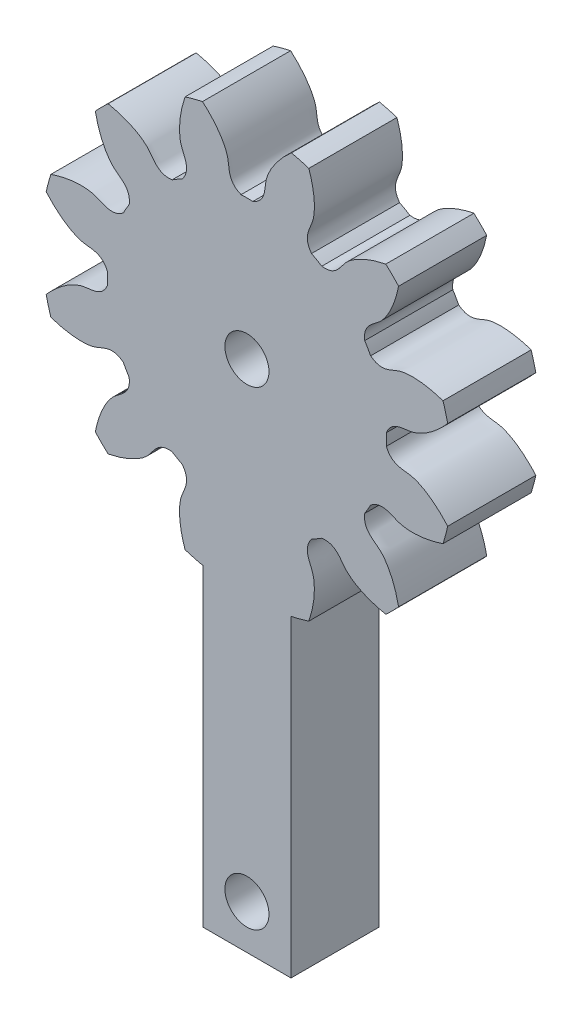
SolidWorks part; units mm, degrees
ref_plane "前视基准面" through (0, 0, 0) normal (0, 0, 1) x (1, 0, 0)
ref_plane "上视基准面" through (0, 0, 0) normal (0, 1, 0) x (1, 0, 0)
ref_plane "右视基准面" through (0, 0, 0) normal (1, 0, 0) x (0, 0, -1)
sketch "草图1" plane through (0, 0, 0) normal (0, 0, 1) x (1, 0, 0)
  circle A0 centre (0, 0) radius 14
extrude "凸台-拉伸1" add sketch "草图1" along normal blind 30
ref_axis "基准轴1" through (0, 0, -1.5) along (0, 0, 1)
sketch "草图2" plane through (0, 0, 0) normal (0, 0, 1) x (1, 0, 0)
  line L0 (0, 0) -> (0, 14) construction
  circle A0 centre (0, 0) radius 14 construction
  arc A1 (0.4017, 9.4915) -> (-0.4017, 9.4915) centre (0, 0) ccw
  arc A2 (6.9952, 15.7899) -> (-6.9952, 15.7899) centre (0, 0) ccw
  spline S0 degree 3 poles (0.4017, 9.4915) (1.3616, 9.8986) (1.1487, 10.6896) (1.3523, 11.379) (1.3652, 11.4198) (1.3805, 11.4647) (1.3981, 11.5135) (1.4183, 11.5661) (1.4413, 11.6225) (1.4671, 11.6826) (1.4961, 11.7462) (1.5282, 11.8133) (1.5637, 11.8838) (1.6028, 11.9576) (1.6455, 12.0345) (1.6919, 12.1144) (1.7423, 12.1973) (1.7968, 12.2829) (1.8555, 12.3712) (1.9185, 12.462) (1.9859, 12.5552) (2.0579, 12.6506) (2.1346, 12.7481) (2.2161, 12.8475) (2.3025, 12.9487) (2.3939, 13.0516) (2.4904, 13.1559) (2.5921, 13.2615) (2.6991, 13.3682) (2.8114, 13.4759) (2.9292, 13.5844) (3.0525, 13.6935) (3.1814, 13.803) (3.316, 13.9128) (3.4563, 14.0226) (3.6023, 14.1323) (3.7542, 14.2418) (3.912, 14.3507) (4.0756, 14.4589) (4.2452, 14.5663) (4.4208, 14.6726) (4.6024, 14.7776) (4.79, 14.8811) (4.9836, 14.983) (5.1832, 15.083) (5.3889, 15.1809) (5.6006, 15.2765) (5.8183, 15.3697) (6.042, 15.4602) (6.2717, 15.5478) (6.5888, 15.6615) (6.8312, 15.7402) (6.9952, 15.7899) knots 0 0 0 0 0.218015 0.222044 0.226546 0.231522 0.236972 0.242897 0.249295 0.256167 0.263513 0.271332 0.279626 0.288394 0.297636 0.307351 0.317541 0.328204 0.339341 0.350953 0.363038 0.375597 0.38863 0.402137 0.416118 0.430573 0.445502 0.460904 0.476781 0.493132 0.509956 0.527255 0.545027 0.563273 0.581994 0.601188 0.620856 0.640998 0.661614 0.682704 0.704268 0.726305 0.748817 0.771803 0.795262 0.819196 0.843603 0.868484 0.89384 0.919669 0.945972 1 1 1 1
  spline S1 degree 3 poles (-0.4017, 9.4915) (-1.3616, 9.8986) (-1.1487, 10.6896) (-1.3523, 11.379) (-1.3652, 11.4198) (-1.3805, 11.4647) (-1.3981, 11.5135) (-1.4183, 11.5661) (-1.4413, 11.6225) (-1.4671, 11.6826) (-1.4961, 11.7462) (-1.5282, 11.8133) (-1.5637, 11.8838) (-1.6028, 11.9576) (-1.6455, 12.0345) (-1.6919, 12.1144) (-1.7423, 12.1973) (-1.7968, 12.2829) (-1.8555, 12.3712) (-1.9185, 12.462) (-1.9859, 12.5552) (-2.0579, 12.6506) (-2.1346, 12.7481) (-2.2161, 12.8475) (-2.3025, 12.9487) (-2.3939, 13.0516) (-2.4904, 13.1559) (-2.5921, 13.2615) (-2.6991, 13.3682) (-2.8114, 13.4759) (-2.9292, 13.5844) (-3.0525, 13.6935) (-3.1814, 13.803) (-3.316, 13.9128) (-3.4563, 14.0226) (-3.6023, 14.1323) (-3.7542, 14.2418) (-3.912, 14.3507) (-4.0756, 14.4589) (-4.2452, 14.5663) (-4.4208, 14.6726) (-4.6024, 14.7776) (-4.79, 14.8811) (-4.9836, 14.983) (-5.1832, 15.083) (-5.3889, 15.1809) (-5.6006, 15.2765) (-5.8183, 15.3697) (-6.042, 15.4602) (-6.2717, 15.5478) (-6.5888, 15.6615) (-6.8312, 15.7402) (-6.9952, 15.7899) knots 0 0 0 0 0.218015 0.222044 0.226546 0.231522 0.236972 0.242897 0.249295 0.256167 0.263513 0.271332 0.279626 0.288394 0.297636 0.307351 0.317541 0.328204 0.339341 0.350953 0.363038 0.375597 0.38863 0.402137 0.416118 0.430573 0.445502 0.460904 0.476781 0.493132 0.509956 0.527255 0.545027 0.563273 0.581994 0.601188 0.620856 0.640998 0.661614 0.682704 0.704268 0.726305 0.748817 0.771803 0.795262 0.819196 0.843603 0.868484 0.89384 0.919669 0.945972 1 1 1 1
extrude "切除-拉伸1" cut sketch "草图2" along normal through all
pattern_circular "阵列(圆周)1" count 12 every 30 about axis through (0, 0, -1.5) along (0, 0, 1) of "切除-拉伸1"
sketch "草图3" plane through (0, 0, 0) normal (0, 0, 1) x (1, 0, 0)
  circle A0 centre (0, 0) radius 12 construction
  dimension "Dn" = 24
sketch "草图4" plane through (0, 0, 30) normal (0, 0, 1) x (1, 0, 0)
  arc A24 (-4.3979, 8.4207) -> (-5.0936, 8.019) centre (0, 0) ccw
  arc A25 (-9.4547, 10.3251) -> (-10.3251, 9.4547) centre (0, 0) ccw
  arc A26 (-8.019, 5.0936) -> (-8.4207, 4.3979) centre (0, 0) ccw
  arc A27 (-13.3506, 4.2145) -> (-13.6692, 3.0255) centre (0, 0) ccw
  arc A28 (-9.4915, 0.4017) -> (-9.4915, -0.4017) centre (0, 0) ccw
  arc A29 (-13.6692, -3.0255) -> (-13.3506, -4.2145) centre (0, 0) ccw
  arc A30 (-8.4207, -4.3979) -> (-8.019, -5.0936) centre (0, 0) ccw
  arc A31 (-10.3251, -9.4547) -> (-9.4547, -10.3251) centre (0, 0) ccw
  arc A32 (-5.0936, -8.019) -> (-4.3979, -8.4207) centre (0, 0) ccw
  arc A33 (-4.2145, -13.3506) -> (-3.0255, -13.6692) centre (0, 0) ccw
  arc A34 (-0.4017, -9.4915) -> (0.4017, -9.4915) centre (0, 0) ccw
  arc A35 (3.0255, -13.6692) -> (4.2145, -13.3506) centre (0, 0) ccw
  arc A36 (4.3979, -8.4207) -> (5.0936, -8.019) centre (0, 0) ccw
  arc A37 (9.4547, -10.3251) -> (10.3251, -9.4547) centre (0, 0) ccw
  arc A38 (8.019, -5.0936) -> (8.4207, -4.3979) centre (0, 0) ccw
  arc A39 (13.3506, -4.2145) -> (13.6692, -3.0255) centre (0, 0) ccw
  arc A40 (9.4915, -0.4017) -> (9.4915, 0.4017) centre (0, 0) ccw
  arc A41 (13.6692, 3.0255) -> (13.3506, 4.2145) centre (0, 0) ccw
  arc A42 (8.4207, 4.3979) -> (8.019, 5.0936) centre (0, 0) ccw
  arc A43 (10.3251, 9.4547) -> (9.4547, 10.3251) centre (0, 0) ccw
  arc A44 (5.0936, 8.019) -> (4.3979, 8.4207) centre (0, 0) ccw
  arc A45 (4.2145, 13.3506) -> (3.0255, 13.6692) centre (0, 0) ccw
  arc A46 (0.4017, 9.4915) -> (-0.4017, 9.4915) centre (0, 0) ccw
  arc A47 (-3.0255, 13.6692) -> (-4.2145, 13.3506) centre (0, 0) ccw
  arc A48 (-4.3979, 8.4207) -> (-5.0936, 8.019) centre (0, 0) ccw
  arc A49 (-9.4547, 10.3251) -> (-10.3251, 9.4547) centre (0, 0) ccw
  arc A50 (-8.019, 5.0936) -> (-8.4207, 4.3979) centre (0, 0) ccw
  arc A51 (-13.3506, 4.2145) -> (-13.6692, 3.0255) centre (0, 0) ccw
  arc A52 (-9.4915, 0.4017) -> (-9.4915, -0.4017) centre (0, 0) ccw
  arc A53 (-13.6692, -3.0255) -> (-13.3506, -4.2145) centre (0, 0) ccw
  arc A54 (-8.4207, -4.3979) -> (-8.019, -5.0936) centre (0, 0) ccw
  arc A55 (-10.3251, -9.4547) -> (-9.4547, -10.3251) centre (0, 0) ccw
  arc A56 (-5.0936, -8.019) -> (-4.3979, -8.4207) centre (0, 0) ccw
  arc A57 (-4.2145, -13.3506) -> (-3.0255, -13.6692) centre (0, 0) ccw
  arc A58 (-0.4017, -9.4915) -> (0.4017, -9.4915) centre (0, 0) ccw
  arc A59 (3.0255, -13.6692) -> (4.2145, -13.3506) centre (0, 0) ccw
  arc A60 (4.3979, -8.4207) -> (5.0936, -8.019) centre (0, 0) ccw
  arc A61 (9.4547, -10.3251) -> (10.3251, -9.4547) centre (0, 0) ccw
  arc A62 (8.019, -5.0936) -> (8.4207, -4.3979) centre (0, 0) ccw
  arc A63 (13.3506, -4.2145) -> (13.6692, -3.0255) centre (0, 0) ccw
  arc A64 (9.4915, -0.4017) -> (9.4915, 0.4017) centre (0, 0) ccw
  arc A65 (13.6692, 3.0255) -> (13.3506, 4.2145) centre (0, 0) ccw
  arc A66 (8.4207, 4.3979) -> (8.019, 5.0936) centre (0, 0) ccw
  arc A67 (10.3251, 9.4547) -> (9.4547, 10.3251) centre (0, 0) ccw
  arc A68 (5.0936, 8.019) -> (4.3979, 8.4207) centre (0, 0) ccw
  arc A69 (4.2145, 13.3506) -> (3.0255, 13.6692) centre (0, 0) ccw
  arc A70 (0.4017, 9.4915) -> (-0.4017, 9.4915) centre (0, 0) ccw
  arc A71 (-3.0255, 13.6692) -> (-4.2145, 13.3506) centre (0, 0) ccw
  spline S24 degree 3 poles (2734.3549, 2922.0708) (-47.5679, -59.6433) (0.0383, 2.6205) (-6.8721, 9.1892) (-6.9309, 9.2418) (-7.0145, 9.3106) (-7.1151, 9.387) (-7.2335, 9.4697) (-7.3702, 9.5573) (-7.5259, 9.6485) (-7.7011, 9.7419) (-7.8961, 9.8361) (-8.1112, 9.9296) (-8.3468, 10.021) (-8.6028, 10.1087) (-8.8795, 10.1914) (-41.9256, 18.6379) (-125.0183, -186.7572) (3142.6374, 2471.5878) knots -2.297192 -2.297192 -2.297192 -2.297192 0.69442 0.698448 0.707927 0.719301 0.732571 0.747737 0.764798 0.783756 0.804608 0.827357 0.852001 0.878542 0.906977 0.937309 0.969536 11.65638 11.65638 11.65638 11.65638 only from (-5.0936, 8.019) to (-9.4547, 10.3251)
  spline S25 degree 3 poles (-2465.1384, -3147.6919) (184.2368, 127.601) (-19.1156, 41.103) (-10.1508, 8.7386) (-10.0654, 8.4722) (-9.9757, 8.2264) (-9.883, 8.0011) (-9.789, 7.7961) (-9.695, 7.6111) (-9.6025, 7.4457) (-9.5129, 7.2995) (-9.4276, 7.172) (-9.359, 7.0778) (-9.2968, 6.9977) (-9.2418, 6.9309) (-9.1892, 6.8721) (-2.6206, -0.0382) (59.6418, 47.5668) (-2921.9619, -2734.2533) knots -10.476322 -10.476322 -10.476322 -10.476322 0.046814 0.078094 0.107478 0.134965 0.160558 0.184254 0.206055 0.22596 0.243969 0.260083 0.274301 0.280699 0.292073 0.301552 0.30558 3.297155 3.297155 3.297155 3.297155 only from (-10.3251, 9.4547) to (-8.019, 5.0936)
  spline S26 degree 3 poles (906.9854, 3897.7649) (-11.3733, -75.4366) (-1.2771, 2.2886) (-10.546, 4.522) (-10.6233, 4.5381) (-10.7301, 4.556) (-10.8554, 4.5718) (-10.9992, 4.5842) (-11.1614, 4.5917) (-11.3419, 4.5929) (-11.5403, 4.5862) (-11.7563, 4.5702) (-11.9893, 4.5437) (-12.239, 4.505) (-12.5046, 4.453) (-12.7855, 4.3862) (-45.6276, -4.8219) (-14.8904, -224.2456) (1485.81, 3711.7765) knots -2.297192 -2.297192 -2.297192 -2.297192 0.69442 0.698448 0.707927 0.719301 0.732571 0.747737 0.764798 0.783756 0.804608 0.827357 0.852001 0.878542 0.906977 0.937309 0.969536 11.65638 11.65638 11.65638 11.65638 only from (-8.4207, 4.3979) to (-13.3506, 4.2145)
  spline S27 degree 3 poles (-561.0265, -3958.5503) (95.7533, 202.6241) (-37.1061, 26.0384) (-13.1601, 2.4924) (-12.953, 2.3045) (-12.7524, 2.1365) (-12.5595, 1.9877) (-12.3755, 1.8571) (-12.2016, 1.7439) (-12.0389, 1.6469) (-11.8882, 1.5651) (-11.7506, 1.4973) (-11.6441, 1.4501) (-11.5501, 1.4118) (-11.4691, 1.3815) (-11.3941, 1.3568) (-2.2504, -1.3434) (27.868, 71.0149) (-1163.3666, -3828.9137) knots -10.476322 -10.476322 -10.476322 -10.476322 0.046814 0.078094 0.107478 0.134965 0.160558 0.184254 0.206055 0.22596 0.243969 0.260083 0.274301 0.280699 0.292073 0.301552 0.30558 3.297155 3.297155 3.297155 3.297155 only from (-13.6692, 3.0255) to (-9.4915, 0.4017)
  spline S28 degree 3 poles (-1163.4101, 3829.0561) (27.8687, -71.0167) (-2.2503, 1.3434) (-11.3941, -1.3568) (-11.4691, -1.3815) (-11.5705, -1.4194) (-11.687, -1.4684) (-11.8177, -1.5295) (-11.962, -1.6042) (-12.1188, -1.6934) (-12.2873, -1.7984) (-12.4663, -1.9202) (-12.6549, -2.0597) (-12.8518, -2.218) (-13.0558, -2.3959) (-13.2657, -2.5942) (-37.1037, -26.9897) (99.2273, -201.6476) (-569.1391, 3957.3977) knots -2.297192 -2.297192 -2.297192 -2.297192 0.69442 0.698448 0.707927 0.719301 0.732571 0.747737 0.764798 0.783756 0.804608 0.827357 0.852001 0.878542 0.906977 0.937309 0.969536 11.65638 11.65638 11.65638 11.65638 only from (-9.4915, -0.4017) to (-13.6692, -3.0255)
  spline S29 degree 3 poles (1493.412, -3708.7184) (-18.3873, 223.3543) (-45.154, 3.9968) (-12.6432, -4.4215) (-12.3699, -4.4808) (-12.1121, -4.5259) (-11.8707, -4.5584) (-11.6461, -4.5794) (-11.4389, -4.5906) (-11.2494, -4.5932) (-11.078, -4.5887) (-10.925, -4.5786) (-10.8091, -4.5662) (-10.7085, -4.5524) (-10.6233, -4.5381) (-10.546, -4.522) (-1.2772, -2.2886) (-11.3731, 75.4347) (906.9519, -3897.6198) knots -10.476322 -10.476322 -10.476322 -10.476322 0.046814 0.078094 0.107478 0.134965 0.160558 0.184254 0.206055 0.22596 0.243969 0.260083 0.274301 0.280699 0.292073 0.301552 0.30558 3.297155 3.297155 3.297155 3.297155 only from (-13.3506, -4.2145) to (-8.4207, -4.3979)
  spline S30 degree 3 poles (-2922.0708, 2734.3549) (59.6433, -47.5679) (-2.6205, 0.0383) (-9.1892, -6.8721) (-9.2418, -6.9309) (-9.3106, -7.0145) (-9.387, -7.1151) (-9.4697, -7.2335) (-9.5573, -7.3702) (-9.6485, -7.5259) (-9.7419, -7.7011) (-9.8361, -7.8961) (-9.9296, -8.1112) (-10.021, -8.3468) (-10.1087, -8.6028) (-10.1914, -8.8795) (-18.6379, -41.9256) (186.7572, -125.0183) (-2471.5878, 3142.6374) knots -2.297192 -2.297192 -2.297192 -2.297192 0.69442 0.698448 0.707927 0.719301 0.732571 0.747737 0.764798 0.783756 0.804608 0.827357 0.852001 0.878542 0.906977 0.937309 0.969536 11.65638 11.65638 11.65638 11.65638 only from (-8.019, -5.0936) to (-10.3251, -9.4547)
  spline S31 degree 3 poles (3147.6919, -2465.1384) (-127.601, 184.2368) (-41.103, -19.1156) (-8.7386, -10.1508) (-8.4722, -10.0654) (-8.2264, -9.9757) (-8.0011, -9.883) (-7.7961, -9.789) (-7.6111, -9.695) (-7.4457, -9.6025) (-7.2995, -9.5129) (-7.172, -9.4276) (-7.0778, -9.359) (-6.9977, -9.2968) (-6.9309, -9.2418) (-6.8721, -9.1892) (0.0382, -2.6206) (-47.5668, 59.6418) (2734.2533, -2921.9619) knots -10.476322 -10.476322 -10.476322 -10.476322 0.046814 0.078094 0.107478 0.134965 0.160558 0.184254 0.206055 0.22596 0.243969 0.260083 0.274301 0.280699 0.292073 0.301552 0.30558 3.297155 3.297155 3.297155 3.297155 only from (-9.4547, -10.3251) to (-5.0936, -8.019)
  spline S32 degree 3 poles (-3897.7649, 906.9854) (75.4366, -11.3733) (-2.2886, -1.2771) (-4.522, -10.546) (-4.5381, -10.6233) (-4.556, -10.7301) (-4.5718, -10.8554) (-4.5842, -10.9992) (-4.5917, -11.1614) (-4.5929, -11.3419) (-4.5862, -11.5403) (-4.5702, -11.7563) (-4.5437, -11.9893) (-4.505, -12.239) (-4.453, -12.5046) (-4.3862, -12.7855) (4.8219, -45.6276) (224.2456, -14.8904) (-3711.7765, 1485.81) knots -2.297192 -2.297192 -2.297192 -2.297192 0.69442 0.698448 0.707927 0.719301 0.732571 0.747737 0.764798 0.783756 0.804608 0.827357 0.852001 0.878542 0.906977 0.937309 0.969536 11.65638 11.65638 11.65638 11.65638 only from (-4.3979, -8.4207) to (-4.2145, -13.3506)
  spline S33 degree 3 poles (3958.5503, -561.0265) (-202.6241, 95.7533) (-26.0384, -37.1061) (-2.4924, -13.1601) (-2.3045, -12.953) (-2.1365, -12.7524) (-1.9877, -12.5595) (-1.8571, -12.3755) (-1.7439, -12.2016) (-1.6469, -12.0389) (-1.5651, -11.8882) (-1.4973, -11.7506) (-1.4501, -11.6441) (-1.4118, -11.5501) (-1.3815, -11.4691) (-1.3568, -11.3941) (1.3434, -2.2504) (-71.0149, 27.868) (3828.9137, -1163.3666) knots -10.476322 -10.476322 -10.476322 -10.476322 0.046814 0.078094 0.107478 0.134965 0.160558 0.184254 0.206055 0.22596 0.243969 0.260083 0.274301 0.280699 0.292073 0.301552 0.30558 3.297155 3.297155 3.297155 3.297155 only from (-3.0255, -13.6692) to (-0.4017, -9.4915)
  spline S34 degree 3 poles (-3829.0561, -1163.4101) (71.0167, 27.8687) (-1.3434, -2.2503) (1.3568, -11.3941) (1.3815, -11.4691) (1.4194, -11.5705) (1.4684, -11.687) (1.5295, -11.8177) (1.6042, -11.962) (1.6934, -12.1188) (1.7984, -12.2873) (1.9202, -12.4663) (2.0597, -12.6549) (2.218, -12.8518) (2.3959, -13.0558) (2.5942, -13.2657) (26.9897, -37.1037) (201.6476, 99.2273) (-3957.3977, -569.1391) knots -2.297192 -2.297192 -2.297192 -2.297192 0.69442 0.698448 0.707927 0.719301 0.732571 0.747737 0.764798 0.783756 0.804608 0.827357 0.852001 0.878542 0.906977 0.937309 0.969536 11.65638 11.65638 11.65638 11.65638 only from (0.4017, -9.4915) to (3.0255, -13.6692)
  spline S35 degree 3 poles (3708.7184, 1493.412) (-223.3543, -18.3873) (-3.9968, -45.154) (4.4215, -12.6432) (4.4808, -12.3699) (4.5259, -12.1121) (4.5584, -11.8707) (4.5794, -11.6461) (4.5906, -11.4389) (4.5932, -11.2494) (4.5887, -11.078) (4.5786, -10.925) (4.5662, -10.8091) (4.5524, -10.7085) (4.5381, -10.6233) (4.522, -10.546) (2.2886, -1.2772) (-75.4347, -11.3731) (3897.6198, 906.9519) knots -10.476322 -10.476322 -10.476322 -10.476322 0.046814 0.078094 0.107478 0.134965 0.160558 0.184254 0.206055 0.22596 0.243969 0.260083 0.274301 0.280699 0.292073 0.301552 0.30558 3.297155 3.297155 3.297155 3.297155 only from (4.2145, -13.3506) to (4.3979, -8.4207)
  spline S36 degree 3 poles (-2734.3549, -2922.0708) (47.5679, 59.6433) (-0.0383, -2.6205) (6.8721, -9.1892) (6.9309, -9.2418) (7.0145, -9.3106) (7.1151, -9.387) (7.2335, -9.4697) (7.3702, -9.5573) (7.5259, -9.6485) (7.7011, -9.7419) (7.8961, -9.8361) (8.1112, -9.9296) (8.3468, -10.021) (8.6028, -10.1087) (8.8795, -10.1914) (41.9256, -18.6379) (125.0183, 186.7572) (-3142.6374, -2471.5878) knots -2.297192 -2.297192 -2.297192 -2.297192 0.69442 0.698448 0.707927 0.719301 0.732571 0.747737 0.764798 0.783756 0.804608 0.827357 0.852001 0.878542 0.906977 0.937309 0.969536 11.65638 11.65638 11.65638 11.65638 only from (5.0936, -8.019) to (9.4547, -10.3251)
  spline S37 degree 3 poles (2465.1384, 3147.6919) (-184.2368, -127.601) (19.1156, -41.103) (10.1508, -8.7386) (10.0654, -8.4722) (9.9757, -8.2264) (9.883, -8.0011) (9.789, -7.7961) (9.695, -7.6111) (9.6025, -7.4457) (9.5129, -7.2995) (9.4276, -7.172) (9.359, -7.0778) (9.2968, -6.9977) (9.2418, -6.9309) (9.1892, -6.8721) (2.6206, 0.0382) (-59.6418, -47.5668) (2921.9619, 2734.2533) knots -10.476322 -10.476322 -10.476322 -10.476322 0.046814 0.078094 0.107478 0.134965 0.160558 0.184254 0.206055 0.22596 0.243969 0.260083 0.274301 0.280699 0.292073 0.301552 0.30558 3.297155 3.297155 3.297155 3.297155 only from (10.3251, -9.4547) to (8.019, -5.0936)
  spline S38 degree 3 poles (-906.9854, -3897.7649) (11.3733, 75.4366) (1.2771, -2.2886) (10.546, -4.522) (10.6233, -4.5381) (10.7301, -4.556) (10.8554, -4.5718) (10.9992, -4.5842) (11.1614, -4.5917) (11.3419, -4.5929) (11.5403, -4.5862) (11.7563, -4.5702) (11.9893, -4.5437) (12.239, -4.505) (12.5046, -4.453) (12.7855, -4.3862) (45.6276, 4.8219) (14.8904, 224.2456) (-1485.81, -3711.7765) knots -2.297192 -2.297192 -2.297192 -2.297192 0.69442 0.698448 0.707927 0.719301 0.732571 0.747737 0.764798 0.783756 0.804608 0.827357 0.852001 0.878542 0.906977 0.937309 0.969536 11.65638 11.65638 11.65638 11.65638 only from (8.4207, -4.3979) to (13.3506, -4.2145)
  spline S39 degree 3 poles (561.0265, 3958.5503) (-95.7533, -202.6241) (37.1061, -26.0384) (13.1601, -2.4924) (12.953, -2.3045) (12.7524, -2.1365) (12.5595, -1.9877) (12.3755, -1.8571) (12.2016, -1.7439) (12.0389, -1.6469) (11.8882, -1.5651) (11.7506, -1.4973) (11.6441, -1.4501) (11.5501, -1.4118) (11.4691, -1.3815) (11.3941, -1.3568) (2.2504, 1.3434) (-27.868, -71.0149) (1163.3666, 3828.9137) knots -10.476322 -10.476322 -10.476322 -10.476322 0.046814 0.078094 0.107478 0.134965 0.160558 0.184254 0.206055 0.22596 0.243969 0.260083 0.274301 0.280699 0.292073 0.301552 0.30558 3.297155 3.297155 3.297155 3.297155 only from (13.6692, -3.0255) to (9.4915, -0.4017)
  spline S40 degree 3 poles (1163.4101, -3829.0561) (-27.8687, 71.0167) (2.2503, -1.3434) (11.3941, 1.3568) (11.4691, 1.3815) (11.5705, 1.4194) (11.687, 1.4684) (11.8177, 1.5295) (11.962, 1.6042) (12.1188, 1.6934) (12.2873, 1.7984) (12.4663, 1.9202) (12.6549, 2.0597) (12.8518, 2.218) (13.0558, 2.3959) (13.2657, 2.5942) (37.1037, 26.9897) (-99.2273, 201.6476) (569.1391, -3957.3977) knots -2.297192 -2.297192 -2.297192 -2.297192 0.69442 0.698448 0.707927 0.719301 0.732571 0.747737 0.764798 0.783756 0.804608 0.827357 0.852001 0.878542 0.906977 0.937309 0.969536 11.65638 11.65638 11.65638 11.65638 only from (9.4915, 0.4017) to (13.6692, 3.0255)
  spline S41 degree 3 poles (-1493.412, 3708.7184) (18.3873, -223.3543) (45.154, -3.9968) (12.6432, 4.4215) (12.3699, 4.4808) (12.1121, 4.5259) (11.8707, 4.5584) (11.6461, 4.5794) (11.4389, 4.5906) (11.2494, 4.5932) (11.078, 4.5887) (10.925, 4.5786) (10.8091, 4.5662) (10.7085, 4.5524) (10.6233, 4.5381) (10.546, 4.522) (1.2772, 2.2886) (11.3731, -75.4347) (-906.9519, 3897.6198) knots -10.476322 -10.476322 -10.476322 -10.476322 0.046814 0.078094 0.107478 0.134965 0.160558 0.184254 0.206055 0.22596 0.243969 0.260083 0.274301 0.280699 0.292073 0.301552 0.30558 3.297155 3.297155 3.297155 3.297155 only from (13.3506, 4.2145) to (8.4207, 4.3979)
  spline S42 degree 3 poles (2922.0708, -2734.3549) (-59.6433, 47.5679) (2.6205, -0.0383) (9.1892, 6.8721) (9.2418, 6.9309) (9.3106, 7.0145) (9.387, 7.1151) (9.4697, 7.2335) (9.5573, 7.3702) (9.6485, 7.5259) (9.7419, 7.7011) (9.8361, 7.8961) (9.9296, 8.1112) (10.021, 8.3468) (10.1087, 8.6028) (10.1914, 8.8795) (18.6379, 41.9256) (-186.7572, 125.0183) (2471.5878, -3142.6374) knots -2.297192 -2.297192 -2.297192 -2.297192 0.69442 0.698448 0.707927 0.719301 0.732571 0.747737 0.764798 0.783756 0.804608 0.827357 0.852001 0.878542 0.906977 0.937309 0.969536 11.65638 11.65638 11.65638 11.65638 only from (8.019, 5.0936) to (10.3251, 9.4547)
  spline S43 degree 3 poles (-3147.6919, 2465.1384) (127.601, -184.2368) (41.103, 19.1156) (8.7386, 10.1508) (8.4722, 10.0654) (8.2264, 9.9757) (8.0011, 9.883) (7.7961, 9.789) (7.6111, 9.695) (7.4457, 9.6025) (7.2995, 9.5129) (7.172, 9.4276) (7.0778, 9.359) (6.9977, 9.2968) (6.9309, 9.2418) (6.8721, 9.1892) (-0.0382, 2.6206) (47.5668, -59.6418) (-2734.2533, 2921.9619) knots -10.476322 -10.476322 -10.476322 -10.476322 0.046814 0.078094 0.107478 0.134965 0.160558 0.184254 0.206055 0.22596 0.243969 0.260083 0.274301 0.280699 0.292073 0.301552 0.30558 3.297155 3.297155 3.297155 3.297155 only from (9.4547, 10.3251) to (5.0936, 8.019)
  spline S44 degree 3 poles (3897.7649, -906.9854) (-75.4366, 11.3733) (2.2886, 1.2771) (4.522, 10.546) (4.5381, 10.6233) (4.556, 10.7301) (4.5718, 10.8554) (4.5842, 10.9992) (4.5917, 11.1614) (4.5929, 11.3419) (4.5862, 11.5403) (4.5702, 11.7563) (4.5437, 11.9893) (4.505, 12.239) (4.453, 12.5046) (4.3862, 12.7855) (-4.8219, 45.6276) (-224.2456, 14.8904) (3711.7765, -1485.81) knots -2.297192 -2.297192 -2.297192 -2.297192 0.69442 0.698448 0.707927 0.719301 0.732571 0.747737 0.764798 0.783756 0.804608 0.827357 0.852001 0.878542 0.906977 0.937309 0.969536 11.65638 11.65638 11.65638 11.65638 only from (4.3979, 8.4207) to (4.2145, 13.3506)
  spline S45 degree 3 poles (-3958.5503, 561.0265) (202.6241, -95.7533) (26.0384, 37.1061) (2.4924, 13.1601) (2.3045, 12.953) (2.1365, 12.7524) (1.9877, 12.5595) (1.8571, 12.3755) (1.7439, 12.2016) (1.6469, 12.0389) (1.5651, 11.8882) (1.4973, 11.7506) (1.4501, 11.6441) (1.4118, 11.5501) (1.3815, 11.4691) (1.3568, 11.3941) (-1.3434, 2.2504) (71.0149, -27.868) (-3828.9137, 1163.3666) knots -10.476322 -10.476322 -10.476322 -10.476322 0.046814 0.078094 0.107478 0.134965 0.160558 0.184254 0.206055 0.22596 0.243969 0.260083 0.274301 0.280699 0.292073 0.301552 0.30558 3.297155 3.297155 3.297155 3.297155 only from (3.0255, 13.6692) to (0.4017, 9.4915)
  spline S46 degree 3 poles (3829.0561, 1163.4101) (-71.0167, -27.8687) (1.3434, 2.2503) (-1.3568, 11.3941) (-1.3815, 11.4691) (-1.4194, 11.5705) (-1.4684, 11.687) (-1.5295, 11.8177) (-1.6042, 11.962) (-1.6934, 12.1188) (-1.7984, 12.2873) (-1.9202, 12.4663) (-2.0597, 12.6549) (-2.218, 12.8518) (-2.3959, 13.0558) (-2.5942, 13.2657) (-26.9897, 37.1037) (-201.6476, -99.2273) (3957.3977, 569.1391) knots -2.297192 -2.297192 -2.297192 -2.297192 0.69442 0.698448 0.707927 0.719301 0.732571 0.747737 0.764798 0.783756 0.804608 0.827357 0.852001 0.878542 0.906977 0.937309 0.969536 11.65638 11.65638 11.65638 11.65638 only from (-0.4017, 9.4915) to (-3.0255, 13.6692)
  spline S47 degree 3 poles (-3708.7184, -1493.412) (223.3543, 18.3873) (3.9968, 45.154) (-4.4215, 12.6432) (-4.4808, 12.3699) (-4.5259, 12.1121) (-4.5584, 11.8707) (-4.5794, 11.6461) (-4.5906, 11.4389) (-4.5932, 11.2494) (-4.5887, 11.078) (-4.5786, 10.925) (-4.5662, 10.8091) (-4.5524, 10.7085) (-4.5381, 10.6233) (-4.522, 10.546) (-2.2886, 1.2772) (75.4347, 11.3731) (-3897.6198, -906.9519) knots -10.476322 -10.476322 -10.476322 -10.476322 0.046814 0.078094 0.107478 0.134965 0.160558 0.184254 0.206055 0.22596 0.243969 0.260083 0.274301 0.280699 0.292073 0.301552 0.30558 3.297155 3.297155 3.297155 3.297155 only from (-4.2145, 13.3506) to (-4.3979, 8.4207)
  spline S48 degree 3 poles (-5.0936, 8.019) (-6.1285, 7.8917) (-6.3397, 8.6831) (-6.8721, 9.1892) (-6.9309, 9.2418) (-7.0145, 9.3106) (-7.1151, 9.387) (-7.2335, 9.4697) (-7.3702, 9.5573) (-7.5259, 9.6485) (-7.7011, 9.7419) (-7.8961, 9.8361) (-8.1112, 9.9296) (-8.3468, 10.021) (-8.6028, 10.1087) (-8.8795, 10.1914) (-9.1655, 10.2645) (-9.3599, 10.3064) (-9.4547, 10.3251) knots 0.476404 0.476404 0.476404 0.476404 0.69442 0.698448 0.707927 0.719301 0.732571 0.747737 0.764798 0.783756 0.804608 0.827357 0.852001 0.878542 0.906977 0.937309 0.969536 1 1 1 1
  spline S49 degree 3 poles (-10.3251, 9.4547) (-10.2963, 9.309) (-10.2418, 9.0672) (-10.1508, 8.7386) (-10.0654, 8.4722) (-9.9757, 8.2264) (-9.883, 8.0011) (-9.789, 7.7961) (-9.695, 7.6111) (-9.6025, 7.4457) (-9.5129, 7.2995) (-9.4276, 7.172) (-9.359, 7.0778) (-9.2968, 6.9977) (-9.2418, 6.9309) (-9.1892, 6.8721) (-8.6831, 6.3397) (-7.8917, 6.1285) (-8.019, 5.0936) knots 0 0 0 0 0.046814 0.078094 0.107478 0.134965 0.160558 0.184254 0.206055 0.22596 0.243969 0.260083 0.274301 0.280699 0.292073 0.301552 0.30558 0.523596 0.523596 0.523596 0.523596
  spline S50 degree 3 poles (-8.4207, 4.3979) (-9.2532, 3.7701) (-9.8319, 4.35) (-10.546, 4.522) (-10.6233, 4.5381) (-10.7301, 4.556) (-10.8554, 4.5718) (-10.9992, 4.5842) (-11.1614, 4.5917) (-11.3419, 4.5929) (-11.5403, 4.5862) (-11.7563, 4.5702) (-11.9893, 4.5437) (-12.239, 4.505) (-12.5046, 4.453) (-12.7855, 4.3862) (-13.0698, 4.3065) (-13.2591, 4.2457) (-13.3506, 4.2145) knots 0.476404 0.476404 0.476404 0.476404 0.69442 0.698448 0.707927 0.719301 0.732571 0.747737 0.764798 0.783756 0.804608 0.827357 0.852001 0.878542 0.906977 0.937309 0.969536 1 1 1 1
  spline S51 degree 3 poles (-13.6692, 3.0255) (-13.5714, 2.9137) (-13.4033, 2.7316) (-13.1601, 2.4924) (-12.953, 2.3045) (-12.7524, 2.1365) (-12.5595, 1.9877) (-12.3755, 1.8571) (-12.2016, 1.7439) (-12.0389, 1.6469) (-11.8882, 1.5651) (-11.7506, 1.4973) (-11.6441, 1.4501) (-11.5501, 1.4118) (-11.4691, 1.3815) (-11.3941, 1.3568) (-10.6896, 1.1487) (-9.8986, 1.3616) (-9.4915, 0.4017) knots 0 0 0 0 0.046814 0.078094 0.107478 0.134965 0.160558 0.184254 0.206055 0.22596 0.243969 0.260083 0.274301 0.280699 0.292073 0.301552 0.30558 0.523596 0.523596 0.523596 0.523596
  spline S52 degree 3 poles (-9.4915, -0.4017) (-9.8986, -1.3616) (-10.6896, -1.1487) (-11.3941, -1.3568) (-11.4691, -1.3815) (-11.5705, -1.4194) (-11.687, -1.4684) (-11.8177, -1.5295) (-11.962, -1.6042) (-12.1188, -1.6934) (-12.2873, -1.7984) (-12.4663, -1.9202) (-12.6549, -2.0597) (-12.8518, -2.218) (-13.0558, -2.3959) (-13.2657, -2.5942) (-13.472, -2.8053) (-13.6056, -2.9527) (-13.6692, -3.0255) knots 0.476404 0.476404 0.476404 0.476404 0.69442 0.698448 0.707927 0.719301 0.732571 0.747737 0.764798 0.783756 0.804608 0.827357 0.852001 0.878542 0.906977 0.937309 0.969536 1 1 1 1
  spline S53 degree 3 poles (-13.3506, -4.2145) (-13.21, -4.2624) (-12.9734, -4.3361) (-12.6432, -4.4215) (-12.3699, -4.4808) (-12.1121, -4.5259) (-11.8707, -4.5584) (-11.6461, -4.5794) (-11.4389, -4.5906) (-11.2494, -4.5932) (-11.078, -4.5887) (-10.925, -4.5786) (-10.8091, -4.5662) (-10.7085, -4.5524) (-10.6233, -4.5381) (-10.546, -4.522) (-9.8319, -4.35) (-9.2532, -3.7701) (-8.4207, -4.3979) knots 0 0 0 0 0.046814 0.078094 0.107478 0.134965 0.160558 0.184254 0.206055 0.22596 0.243969 0.260083 0.274301 0.280699 0.292073 0.301552 0.30558 0.523596 0.523596 0.523596 0.523596
  spline S54 degree 3 poles (-8.019, -5.0936) (-7.8917, -6.1285) (-8.6831, -6.3397) (-9.1892, -6.8721) (-9.2418, -6.9309) (-9.3106, -7.0145) (-9.387, -7.1151) (-9.4697, -7.2335) (-9.5573, -7.3702) (-9.6485, -7.5259) (-9.7419, -7.7011) (-9.8361, -7.8961) (-9.9296, -8.1112) (-10.021, -8.3468) (-10.1087, -8.6028) (-10.1914, -8.8795) (-10.2645, -9.1655) (-10.3064, -9.3599) (-10.3251, -9.4547) knots 0.476404 0.476404 0.476404 0.476404 0.69442 0.698448 0.707927 0.719301 0.732571 0.747737 0.764798 0.783756 0.804608 0.827357 0.852001 0.878542 0.906977 0.937309 0.969536 1 1 1 1
  spline S55 degree 3 poles (-9.4547, -10.3251) (-9.309, -10.2963) (-9.0672, -10.2418) (-8.7386, -10.1508) (-8.4722, -10.0654) (-8.2264, -9.9757) (-8.0011, -9.883) (-7.7961, -9.789) (-7.6111, -9.695) (-7.4457, -9.6025) (-7.2995, -9.5129) (-7.172, -9.4276) (-7.0778, -9.359) (-6.9977, -9.2968) (-6.9309, -9.2418) (-6.8721, -9.1892) (-6.3397, -8.6831) (-6.1285, -7.8917) (-5.0936, -8.019) knots 0 0 0 0 0.046814 0.078094 0.107478 0.134965 0.160558 0.184254 0.206055 0.22596 0.243969 0.260083 0.274301 0.280699 0.292073 0.301552 0.30558 0.523596 0.523596 0.523596 0.523596
  spline S56 degree 3 poles (-4.3979, -8.4207) (-3.7701, -9.2532) (-4.35, -9.8319) (-4.522, -10.546) (-4.5381, -10.6233) (-4.556, -10.7301) (-4.5718, -10.8554) (-4.5842, -10.9992) (-4.5917, -11.1614) (-4.5929, -11.3419) (-4.5862, -11.5403) (-4.5702, -11.7563) (-4.5437, -11.9893) (-4.505, -12.239) (-4.453, -12.5046) (-4.3862, -12.7855) (-4.3065, -13.0698) (-4.2457, -13.2591) (-4.2145, -13.3506) knots 0.476404 0.476404 0.476404 0.476404 0.69442 0.698448 0.707927 0.719301 0.732571 0.747737 0.764798 0.783756 0.804608 0.827357 0.852001 0.878542 0.906977 0.937309 0.969536 1 1 1 1
  spline S57 degree 3 poles (-3.0255, -13.6692) (-2.9137, -13.5714) (-2.7316, -13.4033) (-2.4924, -13.1601) (-2.3045, -12.953) (-2.1365, -12.7524) (-1.9877, -12.5595) (-1.8571, -12.3755) (-1.7439, -12.2016) (-1.6469, -12.0389) (-1.5651, -11.8882) (-1.4973, -11.7506) (-1.4501, -11.6441) (-1.4118, -11.5501) (-1.3815, -11.4691) (-1.3568, -11.3941) (-1.1487, -10.6896) (-1.3616, -9.8986) (-0.4017, -9.4915) knots 0 0 0 0 0.046814 0.078094 0.107478 0.134965 0.160558 0.184254 0.206055 0.22596 0.243969 0.260083 0.274301 0.280699 0.292073 0.301552 0.30558 0.523596 0.523596 0.523596 0.523596
  spline S58 degree 3 poles (0.4017, -9.4915) (1.3616, -9.8986) (1.1487, -10.6896) (1.3568, -11.3941) (1.3815, -11.4691) (1.4194, -11.5705) (1.4684, -11.687) (1.5295, -11.8177) (1.6042, -11.962) (1.6934, -12.1188) (1.7984, -12.2873) (1.9202, -12.4663) (2.0597, -12.6549) (2.218, -12.8518) (2.3959, -13.0558) (2.5942, -13.2657) (2.8053, -13.472) (2.9527, -13.6056) (3.0255, -13.6692) knots 0.476404 0.476404 0.476404 0.476404 0.69442 0.698448 0.707927 0.719301 0.732571 0.747737 0.764798 0.783756 0.804608 0.827357 0.852001 0.878542 0.906977 0.937309 0.969536 1 1 1 1
  spline S59 degree 3 poles (4.2145, -13.3506) (4.2624, -13.21) (4.3361, -12.9734) (4.4215, -12.6432) (4.4808, -12.3699) (4.5259, -12.1121) (4.5584, -11.8707) (4.5794, -11.6461) (4.5906, -11.4389) (4.5932, -11.2494) (4.5887, -11.078) (4.5786, -10.925) (4.5662, -10.8091) (4.5524, -10.7085) (4.5381, -10.6233) (4.522, -10.546) (4.35, -9.8319) (3.7701, -9.2532) (4.3979, -8.4207) knots 0 0 0 0 0.046814 0.078094 0.107478 0.134965 0.160558 0.184254 0.206055 0.22596 0.243969 0.260083 0.274301 0.280699 0.292073 0.301552 0.30558 0.523596 0.523596 0.523596 0.523596
  spline S60 degree 3 poles (5.0936, -8.019) (6.1285, -7.8917) (6.3397, -8.6831) (6.8721, -9.1892) (6.9309, -9.2418) (7.0145, -9.3106) (7.1151, -9.387) (7.2335, -9.4697) (7.3702, -9.5573) (7.5259, -9.6485) (7.7011, -9.7419) (7.8961, -9.8361) (8.1112, -9.9296) (8.3468, -10.021) (8.6028, -10.1087) (8.8795, -10.1914) (9.1655, -10.2645) (9.3599, -10.3064) (9.4547, -10.3251) knots 0.476404 0.476404 0.476404 0.476404 0.69442 0.698448 0.707927 0.719301 0.732571 0.747737 0.764798 0.783756 0.804608 0.827357 0.852001 0.878542 0.906977 0.937309 0.969536 1 1 1 1
  spline S61 degree 3 poles (10.3251, -9.4547) (10.2963, -9.309) (10.2418, -9.0672) (10.1508, -8.7386) (10.0654, -8.4722) (9.9757, -8.2264) (9.883, -8.0011) (9.789, -7.7961) (9.695, -7.6111) (9.6025, -7.4457) (9.5129, -7.2995) (9.4276, -7.172) (9.359, -7.0778) (9.2968, -6.9977) (9.2418, -6.9309) (9.1892, -6.8721) (8.6831, -6.3397) (7.8917, -6.1285) (8.019, -5.0936) knots 0 0 0 0 0.046814 0.078094 0.107478 0.134965 0.160558 0.184254 0.206055 0.22596 0.243969 0.260083 0.274301 0.280699 0.292073 0.301552 0.30558 0.523596 0.523596 0.523596 0.523596
  spline S62 degree 3 poles (8.4207, -4.3979) (9.2532, -3.7701) (9.8319, -4.35) (10.546, -4.522) (10.6233, -4.5381) (10.7301, -4.556) (10.8554, -4.5718) (10.9992, -4.5842) (11.1614, -4.5917) (11.3419, -4.5929) (11.5403, -4.5862) (11.7563, -4.5702) (11.9893, -4.5437) (12.239, -4.505) (12.5046, -4.453) (12.7855, -4.3862) (13.0698, -4.3065) (13.2591, -4.2457) (13.3506, -4.2145) knots 0.476404 0.476404 0.476404 0.476404 0.69442 0.698448 0.707927 0.719301 0.732571 0.747737 0.764798 0.783756 0.804608 0.827357 0.852001 0.878542 0.906977 0.937309 0.969536 1 1 1 1
  spline S63 degree 3 poles (13.6692, -3.0255) (13.5714, -2.9137) (13.4033, -2.7316) (13.1601, -2.4924) (12.953, -2.3045) (12.7524, -2.1365) (12.5595, -1.9877) (12.3755, -1.8571) (12.2016, -1.7439) (12.0389, -1.6469) (11.8882, -1.5651) (11.7506, -1.4973) (11.6441, -1.4501) (11.5501, -1.4118) (11.4691, -1.3815) (11.3941, -1.3568) (10.6896, -1.1487) (9.8986, -1.3616) (9.4915, -0.4017) knots 0 0 0 0 0.046814 0.078094 0.107478 0.134965 0.160558 0.184254 0.206055 0.22596 0.243969 0.260083 0.274301 0.280699 0.292073 0.301552 0.30558 0.523596 0.523596 0.523596 0.523596
  spline S64 degree 3 poles (9.4915, 0.4017) (9.8986, 1.3616) (10.6896, 1.1487) (11.3941, 1.3568) (11.4691, 1.3815) (11.5705, 1.4194) (11.687, 1.4684) (11.8177, 1.5295) (11.962, 1.6042) (12.1188, 1.6934) (12.2873, 1.7984) (12.4663, 1.9202) (12.6549, 2.0597) (12.8518, 2.218) (13.0558, 2.3959) (13.2657, 2.5942) (13.472, 2.8053) (13.6056, 2.9527) (13.6692, 3.0255) knots 0.476404 0.476404 0.476404 0.476404 0.69442 0.698448 0.707927 0.719301 0.732571 0.747737 0.764798 0.783756 0.804608 0.827357 0.852001 0.878542 0.906977 0.937309 0.969536 1 1 1 1
  spline S65 degree 3 poles (13.3506, 4.2145) (13.21, 4.2624) (12.9734, 4.3361) (12.6432, 4.4215) (12.3699, 4.4808) (12.1121, 4.5259) (11.8707, 4.5584) (11.6461, 4.5794) (11.4389, 4.5906) (11.2494, 4.5932) (11.078, 4.5887) (10.925, 4.5786) (10.8091, 4.5662) (10.7085, 4.5524) (10.6233, 4.5381) (10.546, 4.522) (9.8319, 4.35) (9.2532, 3.7701) (8.4207, 4.3979) knots 0 0 0 0 0.046814 0.078094 0.107478 0.134965 0.160558 0.184254 0.206055 0.22596 0.243969 0.260083 0.274301 0.280699 0.292073 0.301552 0.30558 0.523596 0.523596 0.523596 0.523596
  spline S66 degree 3 poles (8.019, 5.0936) (7.8917, 6.1285) (8.6831, 6.3397) (9.1892, 6.8721) (9.2418, 6.9309) (9.3106, 7.0145) (9.387, 7.1151) (9.4697, 7.2335) (9.5573, 7.3702) (9.6485, 7.5259) (9.7419, 7.7011) (9.8361, 7.8961) (9.9296, 8.1112) (10.021, 8.3468) (10.1087, 8.6028) (10.1914, 8.8795) (10.2645, 9.1655) (10.3064, 9.3599) (10.3251, 9.4547) knots 0.476404 0.476404 0.476404 0.476404 0.69442 0.698448 0.707927 0.719301 0.732571 0.747737 0.764798 0.783756 0.804608 0.827357 0.852001 0.878542 0.906977 0.937309 0.969536 1 1 1 1
  spline S67 degree 3 poles (9.4547, 10.3251) (9.309, 10.2963) (9.0672, 10.2418) (8.7386, 10.1508) (8.4722, 10.0654) (8.2264, 9.9757) (8.0011, 9.883) (7.7961, 9.789) (7.6111, 9.695) (7.4457, 9.6025) (7.2995, 9.5129) (7.172, 9.4276) (7.0778, 9.359) (6.9977, 9.2968) (6.9309, 9.2418) (6.8721, 9.1892) (6.3397, 8.6831) (6.1285, 7.8917) (5.0936, 8.019) knots 0 0 0 0 0.046814 0.078094 0.107478 0.134965 0.160558 0.184254 0.206055 0.22596 0.243969 0.260083 0.274301 0.280699 0.292073 0.301552 0.30558 0.523596 0.523596 0.523596 0.523596
  spline S68 degree 3 poles (4.3979, 8.4207) (3.7701, 9.2532) (4.35, 9.8319) (4.522, 10.546) (4.5381, 10.6233) (4.556, 10.7301) (4.5718, 10.8554) (4.5842, 10.9992) (4.5917, 11.1614) (4.5929, 11.3419) (4.5862, 11.5403) (4.5702, 11.7563) (4.5437, 11.9893) (4.505, 12.239) (4.453, 12.5046) (4.3862, 12.7855) (4.3065, 13.0698) (4.2457, 13.2591) (4.2145, 13.3506) knots 0.476404 0.476404 0.476404 0.476404 0.69442 0.698448 0.707927 0.719301 0.732571 0.747737 0.764798 0.783756 0.804608 0.827357 0.852001 0.878542 0.906977 0.937309 0.969536 1 1 1 1
  spline S69 degree 3 poles (3.0255, 13.6692) (2.9137, 13.5714) (2.7316, 13.4033) (2.4924, 13.1601) (2.3045, 12.953) (2.1365, 12.7524) (1.9877, 12.5595) (1.8571, 12.3755) (1.7439, 12.2016) (1.6469, 12.0389) (1.5651, 11.8882) (1.4973, 11.7506) (1.4501, 11.6441) (1.4118, 11.5501) (1.3815, 11.4691) (1.3568, 11.3941) (1.1487, 10.6896) (1.3616, 9.8986) (0.4017, 9.4915) knots 0 0 0 0 0.046814 0.078094 0.107478 0.134965 0.160558 0.184254 0.206055 0.22596 0.243969 0.260083 0.274301 0.280699 0.292073 0.301552 0.30558 0.523596 0.523596 0.523596 0.523596
  spline S70 degree 3 poles (-0.4017, 9.4915) (-1.3616, 9.8986) (-1.1487, 10.6896) (-1.3568, 11.3941) (-1.3815, 11.4691) (-1.4194, 11.5705) (-1.4684, 11.687) (-1.5295, 11.8177) (-1.6042, 11.962) (-1.6934, 12.1188) (-1.7984, 12.2873) (-1.9202, 12.4663) (-2.0597, 12.6549) (-2.218, 12.8518) (-2.3959, 13.0558) (-2.5942, 13.2657) (-2.8053, 13.472) (-2.9527, 13.6056) (-3.0255, 13.6692) knots 0.476404 0.476404 0.476404 0.476404 0.69442 0.698448 0.707927 0.719301 0.732571 0.747737 0.764798 0.783756 0.804608 0.827357 0.852001 0.878542 0.906977 0.937309 0.969536 1 1 1 1
  spline S71 degree 3 poles (-4.2145, 13.3506) (-4.2624, 13.21) (-4.3361, 12.9734) (-4.4215, 12.6432) (-4.4808, 12.3699) (-4.5259, 12.1121) (-4.5584, 11.8707) (-4.5794, 11.6461) (-4.5906, 11.4389) (-4.5932, 11.2494) (-4.5887, 11.078) (-4.5786, 10.925) (-4.5662, 10.8091) (-4.5524, 10.7085) (-4.5381, 10.6233) (-4.522, 10.546) (-4.35, 9.8319) (-3.7701, 9.2532) (-4.3979, 8.4207) knots 0 0 0 0 0.046814 0.078094 0.107478 0.134965 0.160558 0.184254 0.206055 0.22596 0.243969 0.260083 0.274301 0.280699 0.292073 0.301552 0.30558 0.523596 0.523596 0.523596 0.523596
  dimension "D1" = 0
extrude "切除-拉伸2" cut sketch "草图4" against normal blind 24
sketch "草图5" plane through (0, 0, 6) normal (0, 0, 1) x (1, 0, 0)
  line L0 (0, 0) -> (0, -9.5) construction
  line L1 (3, -5) -> (-3, -5) construction
  line L2 (-3, -5) -> (-3, -35) construction
  line L3 (-3, -35) -> (3, -35) construction
  line L4 (3, -5) -> (3, -35) construction
  line L5 (0, -5) -> (-3, -5)
  line L6 (-3, -5) -> (-3, -35)
  line L7 (-3, -35) -> (3, -35)
  line L8 (3, -35) -> (3, -5)
  line L9 (3, -5) -> (0, -5)
  arc A1 (-0.4017, -9.4915) -> (0.4017, -9.4915) centre (0, 0) ccw construction
  point P12 (0, -35)
  point P13 (0, -5)
  dimension "D2" = 5
  dimension "D3" = 30
  dimension "D4" = 3
extrude "凸台-拉伸2" add sketch "草图5" against normal blind 6
sketch "草图6" plane through (0, 0, 6) normal (0, 0, 1) x (1, 0, 0)
  circle A0 centre (0, 0) radius 1.5
  dimension "D1" = 3
extrude "切除-拉伸3" cut sketch "草图6" against normal blind 6
sketch "草图7" plane through (0, 0, 6) normal (0, 0, 1) x (1, 0, 0)
  line L0 (0, -35) -> (0, -32) construction
  line L1 (-3, -35) -> (3, -35) construction
  circle A0 centre (0, -32) radius 1.5
  dimension "D1" = 3
  dimension "D2" = 3
extrude "切除-拉伸4" cut sketch "草图7" against normal blind 6
